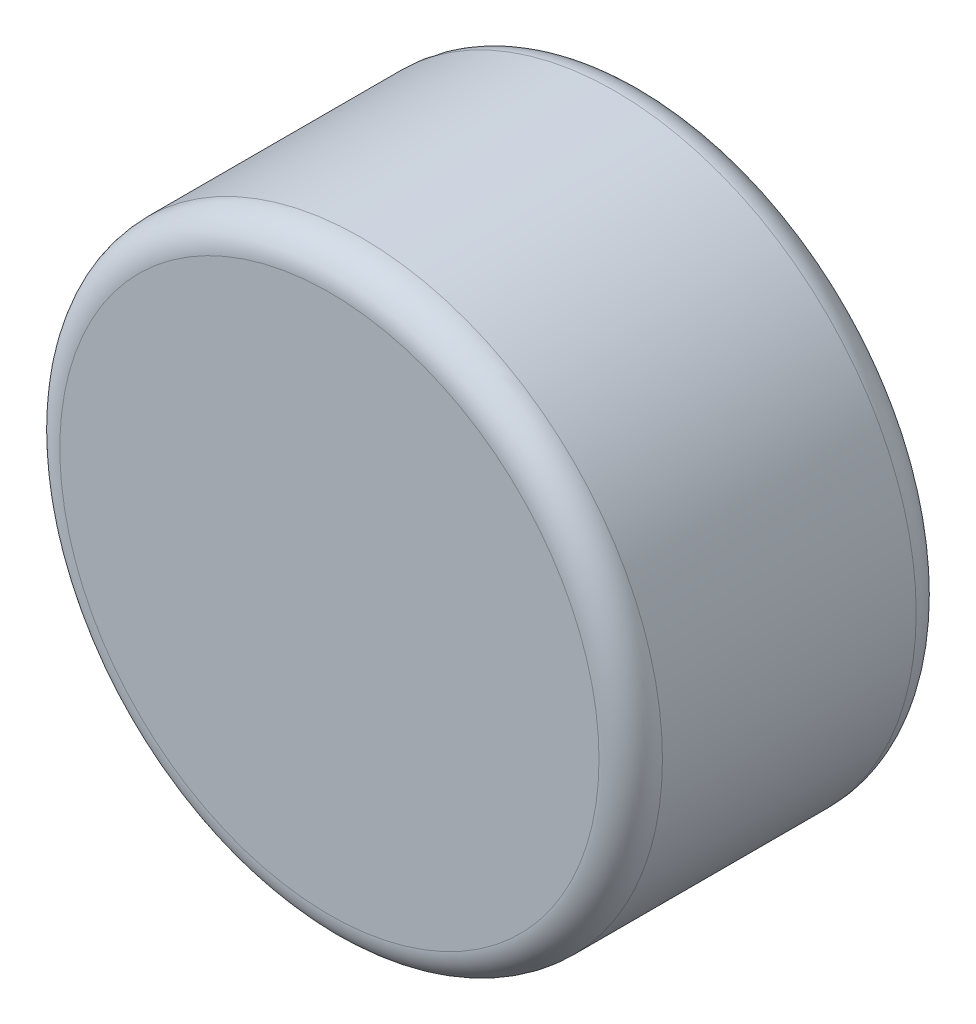
SolidWorks part; units mm, degrees
ref_plane "Front Plane" through (0, 0, 0) normal (0, 0, 1) x (1, 0, 0)
ref_plane "Top Plane" through (0, 0, 0) normal (0, 1, 0) x (1, 0, 0)
ref_plane "Right Plane" through (0, 0, 0) normal (1, 0, 0) x (0, 0, -1)
sketch "Sketch1" plane through (0, 0, 0) normal (0, 0, 1) x (1, 0, 0)
  circle A0 centre (0, 0) radius 47.5
  dimension "D1" = 95
extrude "Boss-Extrude1" add sketch "Sketch1" along normal blind 50
fillet "Fillet1" radius 5 2 edges at (47.5, 0, 0) (47.5, 0, 50)
ref_axis "Central Axis" through (0, 0, 45) along (0, 0, -1)
